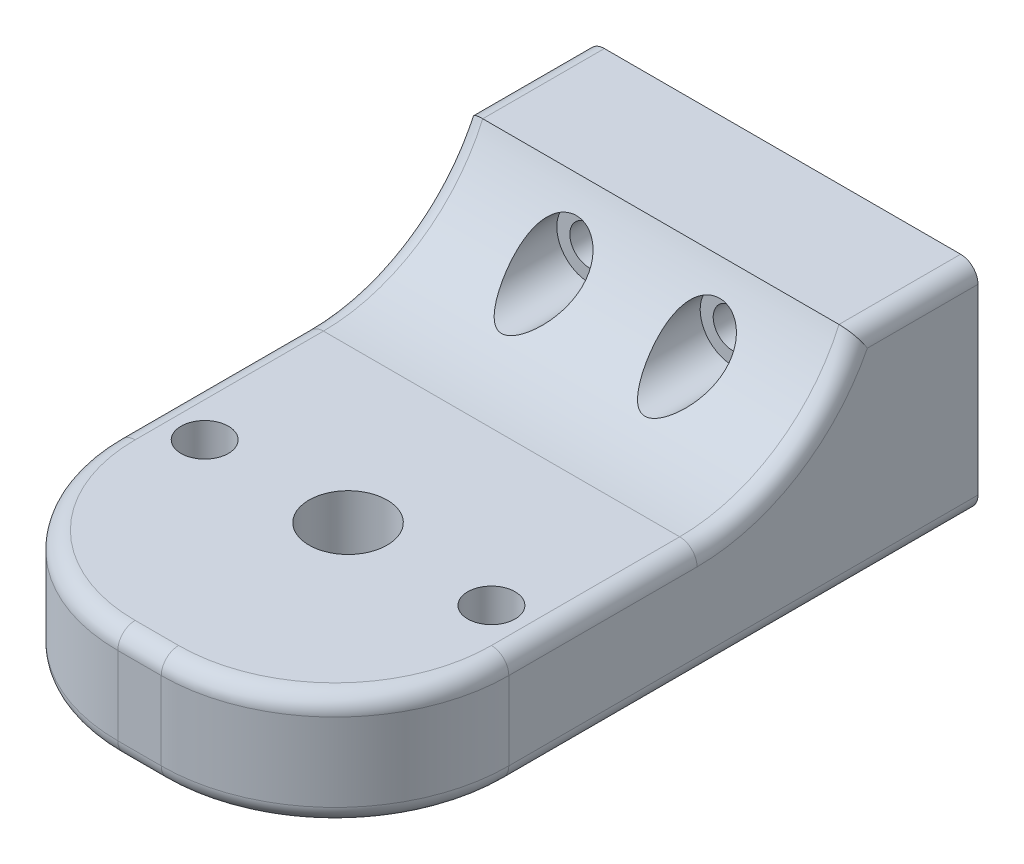
SolidWorks part; units mm, degrees
material "ABS"
ref_plane "Front Plane" through (0, 0, 0) normal (0, 0, 1) x (1, 0, 0)
ref_plane "Top Plane" through (0, 0, 0) normal (0, 1, 0) x (1, 0, 0)
ref_plane "Right Plane" through (0, 0, 0) normal (1, 0, 0) x (0, 0, -1)
sketch "Sketch1" plane through (0, 0, 0) normal (0, 0, 1) x (1, 0, 0)
  line L0 (0, -12.5) -> (0, 12.5) construction
  line L2 (-22.5, 12.5) -> (22.5, 12.5)
  line L3 (-22.5, 12.5) -> (-22.5, -12.5)
  line L4 (-22.5, -12.5) -> (22.5, -12.5)
  line L5 (22.5, 12.5) -> (22.5, -12.5)
  line L6 (-22.5, 12.5) -> (22.5, -12.5) construction
  line L7 (-22.5, -12.5) -> (22.5, 12.5) construction
  circle A0 centre (-8.25, 6) radius 2.225
  circle A1 centre (8.25, 6) radius 2.225
  point P7 (0, 0)
  dimension "D1" = 4.45
  dimension "D2" = 16.5
  dimension "D3" = 45
  dimension "D4" = 25
  dimension "D5" = 6
extrude "Boss-Extrude1" add sketch "Sketch1" along normal blind 74
sketch "Sketch2" plane through (0, -12.5, 0) normal (0, -1, 0) x (1, 0, 0)
  line L0 (0, 74) -> (0, 0) construction
  line L3 (-22.5, 74) -> (22.5, 74) construction
  circle A0 centre (0, 50) radius 4.5
  circle A1 centre (-16.5, 50) radius 2.725
  circle A2 centre (16.5, 50) radius 2.725
  dimension "D1" = 9
  dimension "D4" = 5.45
  dimension "D2" = 50
  dimension "D3" = 33
extrude "Cut-Extrude1" cut sketch "Sketch2" against normal through all
sketch "Sketch3" plane through (0, 0, 74) normal (0, 0, 1) x (1, 0, 0)
  line L0 (22.5, -12.5) -> (22.5, 12.5) construction
  line L1 (-22.5, 12.5) -> (22.5, 12.5)
  line L2 (-22.5, 12.5) -> (-22.5, 0.5)
  line L3 (-22.5, 0.5) -> (22.5, 0.5)
  line L4 (22.5, 12.5) -> (22.5, 0.5)
  dimension "D1" = 12
extrude "Cut-Extrude2" cut sketch "Sketch3" against normal blind 60
sketch "Sketch4" plane through (0, 0, 14) normal (0, 0, 1) x (1, 0, 0)
  circle A0 centre (-8.25, 6) radius 3.725
  circle A1 centre (8.25, 6) radius 3.725
  dimension "D1" = 7.45
fillet "Fillet4" radius 20 1 edges at (0, 0.5, 14)
extrude "Cut-Extrude4" cut sketch "Sketch4" along normal blind 27
fillet "Fillet5" radius 20 2 edges at (22.5, -6, 74) (-22.5, -6, 74)
fillet "Fillet6" radius 2 14 edges at (22.5, -12.5, 27) (16.6421, -12.5, 68.1421) (0, -12.5, 74) (-16.6421, -12.5, 68.1421) (-22.5, 3.7668, 21.3759) (22.5, 3.7668, 21.3759) (22.5, 0.5, 43.1652) (16.6421, 0.5, 68.1421) (0, 0.5, 74) (-16.6421, 0.5, 68.1421) (22.5, 12.5, 7) (-22.5, -12.5, 27) (-22.5, 0.5, 43.1652) (-22.5, 12.5, 7)
equation "\"D4@Sketch2\"=5+\"print_free@Parameters@Parameters.SLDPRT\""
equation "\"D1@Sketch1\"=4+\"print_free@Parameters@Parameters.SLDPRT\""
equation "\"D1@Sketch4\"=7+\"print_free@Parameters@Parameters.SLDPRT\""
